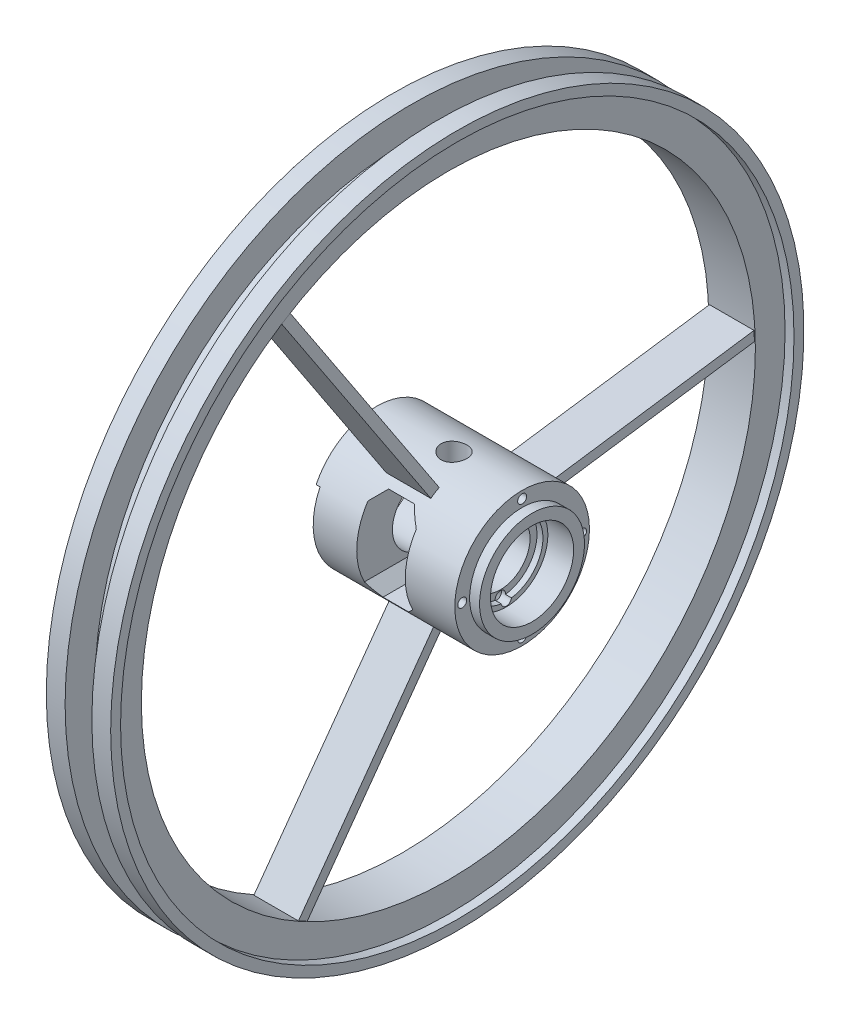
SolidWorks part; units mm, degrees
ref_plane "Front Plane" through (0, 0, 0) normal (0, 0, 1) x (1, 0, 0)
ref_plane "Top Plane" through (0, 0, 0) normal (0, 1, 0) x (1, 0, 0)
ref_plane "Right Plane" through (0, 0, 0) normal (1, 0, 0) x (0, 0, -1)
sketch "Sketch17" plane through (0, 0, 0) normal (0, 0, 1) x (1, 0, 0)
  line L0 (0, 0) -> (156.5215, 0) construction
sketch "Sketch1" plane through (0, 0, 0) normal (1, 0, 0) x (0, 0, -1)
  circle A0 centre (0, 0) radius 68
extrude "Boss-Extrude1" add sketch "Sketch1" along normal blind 157 contours A0
sketch "Sketch2" plane through (0, 0, 0) normal (-1, 0, 0) x (0, 0, 1)
  circle A0 centre (0, 0) radius 26
extrude "Cut-Extrude1" cut sketch "Sketch2" against normal up to next
sketch "Sketch3" plane through (0, 0, 0) normal (-1, 0, 0) x (0, 0, 1)
  line L1 (-68, 30) -> (68, 30)
  line L2 (-68, 30) -> (-68, -68)
  line L3 (-68, -68) -> (68, -68)
  line L4 (68, 30) -> (68, -68)
  circle A2 centre (0, 0) radius 68 construction
  circle A3 centre (0, 0) radius 26 construction
  dimension "D1" = 30
  dimension "D2" = 68
  dimension "D3" = 42
  dimension "D4" = 68
  dimension "D5" = 68
extrude "Cut-Extrude2" cut sketch "Sketch3" against normal blind 4 contours L2 L3 L4 L1
sketch "Sketch4" plane through (4, 0, 0) normal (-1, 0, 0) x (0, 0, 1)
  line L3 (-13.5, 29) -> (13.5, 29)
  arc A2 (13.5, 29) -> (-13.5, 29) centre (0, 0) cw
  dimension "D1" = 27
  dimension "D2" = 29
extrude "Cut-Extrude3" cut sketch "Sketch4" against normal blind 44
sketch "Sketch7" plane through (157, 0, 0) normal (1, 0, 0) x (0, 0, -1)
  circle A0 centre (0, 0) radius 42
extrude "Cut-Extrude4" cut sketch "Sketch7" against normal blind 26
sketch "Sketch8" plane through (131, 0, 0) normal (1, 0, 0) x (0, 0, -1)
  circle A0 centre (0, 0) radius 37
extrude "Cut-Extrude5" cut sketch "Sketch8" against normal blind 6 contours A0
sketch "Sketch9" plane through (125, 0, 0) normal (1, 0, 0) x (0, 0, -1)
  circle A0 centre (0, 0) radius 30
extrude "Cut-Extrude6" cut sketch "Sketch9" against normal blind 30 contours A0
ref_plane "Plane2" through (0, 0, 68) normal (0, 0, 1) x (1, 0, 0)
sketch "Sketch12" plane through (0, 0, 68) normal (0, 0, 1) x (1, 0, 0)
  line L0 (48, 37.576) -> (48, -31.4216)
  line L1 (48, -31.4216) -> (59.3739, -42.7955)
  line L2 (59.3739, -42.7955) -> (85.3739, -42.7955)
  line L3 (85.3739, -42.7955) -> (97, -31.1695)
  line L4 (97, -31.1695) -> (97, 37.3239)
  line L5 (97, 37.3239) -> (85.3739, 48.9499)
  line L6 (85.3739, 48.9499) -> (59.3739, 48.9499)
  line L7 (59.3739, 48.9499) -> (48, 37.576)
  line L8 (157, -68) -> (157, 68) construction
  line L9 (4, 30) -> (4, -68) construction
  dimension "D1" = 60
  dimension "D2" = 44
  dimension "D3" = 26
  dimension "D4" = 26
  dimension "D5" = 135
  dimension "D6" = 135
  dimension "D7" = 135
  dimension "D8" = 135
extrude "Cut-Extrude8" cut sketch "Sketch12" against normal blind 71 contours L0 L1 L2 L3 L4 L5 L6 L7
sketch "Sketch16" plane through (0, 0, 0) normal (-1, 0, 0) x (0, 0, 1)
  line L0 (35.9404, 57.726) -> (61.0246, 30) construction
  line L1 (35.9404, 57.726) -> (0, 68) construction
  arc A0 (61.0246, 30) -> (-61.0246, 30) centre (0, 0) ccw construction
  dimension "D1" = 37.38
  dimension "D2" = 37.3892
ref_plane "Plane5" through (0, 68, 0) normal (0, 1, 0) x (1, 0, 0)
sketch "Sketch23" plane through (0, 68, 0) normal (0, 1, 0) x (1, 0, 0)
  line L0 (0, 0) -> (78.2608, 0) construction
  line L1 (0, 0) -> (156.5215, 0) construction
  point P1 (78.2608, 0)
  point P9 (78.2608, 0)
hole_wizard "Tap Drill for M1.2x0.25 Tap1" positions "Sketch23" profile "Sketch26" hole size "M1.2x0.25" standard "ISO"
sketch "Sketch26" plane through (78.2608, 68, 0) normal (1, 0, 0) x (0, 0, 1)
  line L0 (0, 0) -> (0, 68)
  line L1 (0, 68) -> (13, 68)
  line L2 (13, 68) -> (13, 0)
  line L5 (13, 0) -> (0, 0)
  line L10 (0, 68) -> (-13, 68) construction
  line L11 (0, -6.35) -> (0, 107.95) construction
  dimension "Hole Dia." = 26
  dimension "Hole Depth" = 68
  dimension "Drill Angle" = 180
sketch "Sketch27" plane through (157, 0, 0) normal (1, 0, 0) x (0, 0, -1)
  circle A0 centre (0, 0) radius 68
  circle A1 centre (0, 0) radius 53
  dimension "D1" = 136
  dimension "D2" = 106
extrude "Cut-Extrude9" cut sketch "Sketch27" against normal blind 10
sketch "Sketch29" plane through (147, 0, 0) normal (1, 0, 0) x (0, 0, -1)
  line L0 (0, 68) -> (0, 53) construction
  line L1 (53, 0) -> (68, 0) construction
  line L2 (0, -53) -> (0, -68) construction
  line L3 (-53, 0) -> (-68, 0) construction
  line L4 (-68, 74.8) -> (-68, -74.8) construction
  circle A0 centre (0, 0) radius 53 construction
  circle A1 centre (0, 0) radius 53 construction
  circle A2 centre (0, 0) radius 68 construction
  point P21 (0, 60.5)
  point P23 (60.5, 0)
  point P25 (0, -60.5)
  point P27 (-60.5, 0)
hole_wizard "M8 Clearance Hole1" positions "Sketch29" profile "Sketch30" hole size "M8" standard "ISO"
sketch "Sketch30" plane through (147, 0, 60.5) normal (0, 1, 0) x (0, 0, -1)
  line L0 (0, 0) -> (0, 37.7039)
  line L1 (0, 37.7039) -> (4.5, 35)
  line L2 (4.5, 35) -> (4.5, 0)
  line L5 (4.5, 0) -> (0, 0)
  line L10 (0, 37.7039) -> (-4.5, 35) construction
  line L11 (0, -6.35) -> (0, 107.95) construction
  dimension "Hole Dia." = 9
  dimension "Hole Depth" = 35
  dimension "Drill Angle" = 118
ref_plane "Plane4" through (0, 0, 0) normal (0, 0.5285, -0.8489) x (-1, 0, 0)
sketch "Sketch19" plane through (0, 0, 0) normal (0, 0.5285, -0.8489) x (-1, 0, 0)
  line L3 (-26.5195, 310) -> (-71.5195, 310)
  line L7 (-97, 30.0991) -> (-97, 61.7272) construction
  line L8 (-48, 30.3131) -> (-48, 61.8533) construction
  line L9 (0, 0) -> (-156.5215, 0) construction
  line L10 (-71.5195, 310) -> (-95, 66.5)
  line L11 (-95, 66.5) -> (-50, 66.5)
  line L12 (-50, 66.5) -> (-26.5195, 310)
  line L13 (0, 68) -> (-147, 68) construction
  dimension "D2" = 49
  dimension "D1" = 310
  dimension "D3" = 45
  dimension "D4" = 1.5
  dimension "D5" = 2
sketch "Sketch21" plane through (0, 0, 0) normal (0, 0.5285, -0.8489) x (-1, 0, 0)
  line L0 (-71.5195, 310) -> (-72.5195, 310)
  line L1 (-72.5195, 310) -> (-72.5195, 340)
  line L2 (-72.5195, 340) -> (-81.5195, 340)
  line L3 (-81.5195, 340) -> (-81.5195, 350)
  line L4 (-81.5195, 350) -> (-62.5195, 350)
  line L5 (-16.5195, 350) -> (-16.5195, 340)
  line L6 (-16.5195, 340) -> (-25.5195, 340)
  line L7 (-25.5195, 340) -> (-25.5195, 310)
  line L8 (-25.5195, 310) -> (-26.5195, 310)
  line L11 (-62.5195, 350) -> (-62.5195, 320)
  line L12 (-62.5195, 320) -> (-35.5195, 320)
  line L13 (-35.5195, 320) -> (-35.5195, 350)
  line L14 (-35.5195, 350) -> (-16.5195, 350)
  line L15 (-26.5195, 310) -> (-71.5195, 310) construction
  line L17 (-71.5195, 310) -> (-26.5195, 310)
  dimension "D2" = 10
  dimension "D3" = 10
  dimension "D5" = 1
  dimension "D1" = 10
  dimension "D6" = 10
  dimension "D7" = 10
  dimension "D8" = 65
  dimension "D9" = 27
  dimension "D10" = 9
  dimension "D11" = 40
  dimension "D12" = 40
revolve "Revolve1" add sketch "Sketch21" angle 360 about L0
extrude "Boss-Extrude4" add sketch "Sketch19" along normal mid plane 10
pattern_circular "CirPattern4" count 3 over 360 about axis through (0, 0, 0) along (1, 0, 0) of "Boss-Extrude4"
sketch "Esquisse4" plane through (131, 0, 0) normal (1, 0, 0) x (0, 0, -1)
  line L0 (0, 0) -> (0, -36) construction
  point P11 (0, -36)
  dimension "D1" = 36
  dimension "D2" = 0
hole_wizard "M10 Clearance Hole1" positions "Esquisse4" profile "Esquisse6" hole size "M10" standard "ANSI Metric"
sketch "Esquisse6" plane through (131, -36, 0) normal (0, 1, 0) x (0, 0, -1)
  line L0 (0, 0) -> (0, 13.1545)
  line L1 (0, 13.1545) -> (5.25, 10)
  line L2 (5.25, 10) -> (5.25, 0)
  line L5 (5.25, 0) -> (0, 0)
  line L10 (0, 13.1545) -> (-5.25, 10) construction
  line L11 (0, -6.35) -> (0, 107.95) construction
  dimension "Hole Dia." = 10.5
  dimension "Hole Depth" = 10
  dimension "Drill Angle" = 118
equation "\"D1@Sketch3\"=26+8/2"
equation "\"D2@Sketch3\"=26+\"D3@Sketch3\""
equation "\"D4@Sketch3\"=\"D2@Sketch3\""
equation "\"D5@Sketch3\"=\"D2@Sketch3\""
equation "\"D5@Sketch19\"=(\"D2@Sketch19\"-\"D3@Sketch19\")/2"
equation "\"D10@Sketch21\"=(\"D8@Sketch21\"-\"D9@Sketch21\")/2-10"
equation "\"D12@Sketch21\"=\"D11@Sketch21\""
equation "\"D2@Sketch27\"=\"D1@Sketch27\"-15*2"
